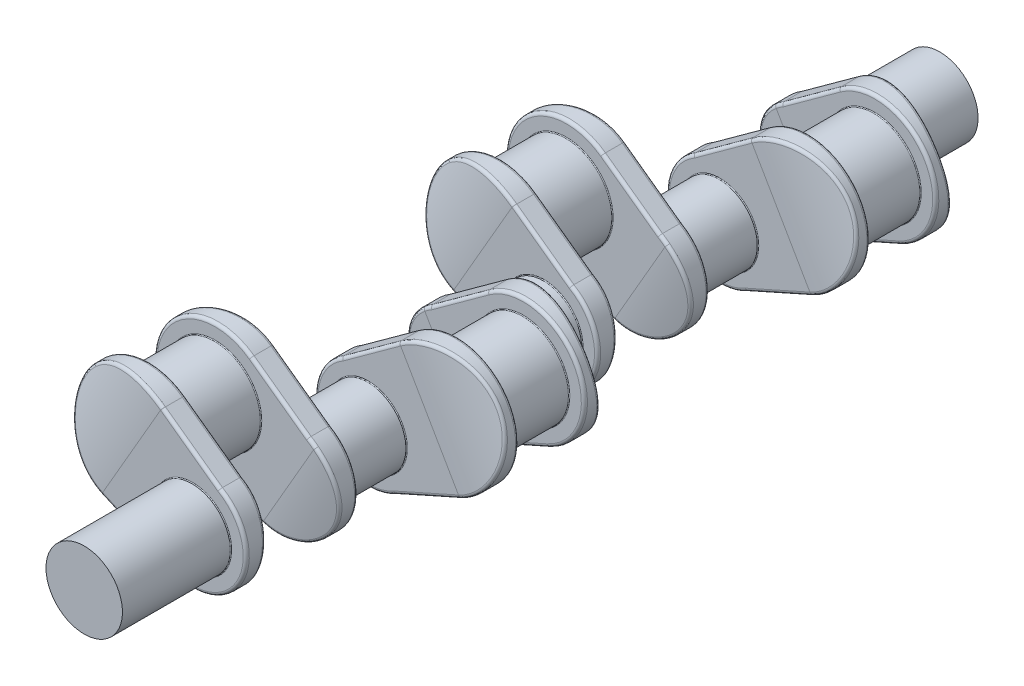
SolidWorks part; units mm, degrees
ref_plane "Front Plane" through (0, 0, 0) normal (0, 0, 1) x (1, 0, 0)
ref_plane "Top Plane" through (0, 0, 0) normal (0, 1, 0) x (1, 0, 0)
ref_plane "Right Plane" through (0, 0, 0) normal (1, 0, 0) x (0, 0, -1)
sketch "Sketch1" plane through (0, 0, 0) normal (0, 0, 1) x (1, 0, 0)
  circle A0 centre (0, 0) radius 38.1
  dimension "D1" = 76.2
extrude "Boss-Extrude1" add sketch "Sketch1" along normal blind 27.31
sketch "Sketch2" plane through (0, 0, 27.31) normal (0, 0, 1) x (1, 0, 0)
  line L0 (-44.45, 63.5) -> (-50.5257, 5.272)
  line L1 (44.45, 63.5) -> (50.5257, 5.272)
  arc A0 (-50.5257, 5.272) -> (50.5257, 5.272) centre (0, 0) ccw
  arc A1 (44.45, 63.5) -> (-44.45, 63.5) centre (0, 63.5) ccw
  circle A2 centre (0, 0) radius 38.1 construction
  point P9 (0, 0)
  dimension "D1" = 12.7
  dimension "D2" = 88.9
  dimension "D3" = 63.5
extrude "Boss-Extrude2" add sketch "Sketch2" along normal blind 19
sketch "Sketch3" plane through (0, 0, 46.31) normal (0, 0, 1) x (1, 0, 0)
  circle A1 centre (0, 63.5) radius 31.75
  dimension "D1" = 63.5
extrude "Boss-Extrude3" add sketch "Sketch3" along normal blind 26.67
sketch "Sketch4" plane through (0, 0, 0) normal (1, 0, 0) x (0, 0, -1)
  line L0 (-46.31, -50.8) -> (-27.31, -50.8) construction
  line L1 (-46.31, 5.272) -> (-58.1018, 5.272)
  line L2 (-58.1018, 5.272) -> (-58.1018, -50.8)
  line L3 (-58.1018, -50.8) -> (-36.81, -50.8)
  arc A0 (-46.31, 5.272) -> (-36.81, -50.8) centre (122.6899, 5.064) ccw
  dimension "D1" = 169
extrude "Cut-Extrude1" cut sketch "Sketch4" against normal mid plane 180.67
sketch "Sketch5" plane through (0, 0, 0) normal (1, 0, 0) x (0, 0, -1)
  line L0 (-27.31, 107.95) -> (-46.31, 107.95) construction
  line L1 (-32.31, 107.95) -> (-14.9237, 107.95)
  line L2 (-14.9237, 107.95) -> (-14.9237, 63.5)
  line L3 (-14.9237, 63.5) -> (-27.31, 63.5)
  arc A0 (-27.31, 63.5) -> (-32.31, 107.95) centre (-196.2738, 67.0002) ccw
  dimension "D2" = 169
  dimension "D1" = 5
extrude "Cut-Extrude2" cut sketch "Sketch5" against normal mid plane 180.67
fillet "Fillet1" radius 2.54 10 edges at (-47.4878, 34.386, 27.31) (0, -50.8, 27.31) (-47.4878, 34.386, 46.31) (-50.547, 5.0641, 46.31) (0.0331, -50.8, 36.81) (50.547, 5.0641, 46.31) (3.1078, 107.8412, 32.2829) (47.4878, 34.386, 27.31) (0, 107.95, 46.31) (47.4878, 34.386, 46.31)
fillet "Fillet2" radius 0.64 2 edges at (38.1, 0, 27.31) (31.75, 63.5, 46.31)
mirror "Mirror1" about plane through (0, 0, 0) normal (0, 0, 1) of bodies 105
ref_axis "Axis1" through (0, 63.5, 471.9753) along (0, 0, -1)
pattern_linear "LPattern1" count 4 spacing 145.96 along (0, 0, 1) of bodies 106
move or copy body "Body-Move/Copy1" bodies to move or copy 107 copy no rotation origin (0, 63.5, 0) rotation axis (0, 0, -1) rotation angle 120
move or copy body "Body-Move/Copy2" bodies to move or copy 109 copy no rotation origin (0, 63.5, 0) rotation axis (0, 0, -1) rotation angle 120
move or copy body "Body-Move/Copy3" bodies to move or copy 106 copy no rotation origin (0, 63.5, 0) rotation axis (0, 0, 1) rotation angle 120
move or copy body "Body-Move/Copy4" bodies to move or copy 108 copy no rotation origin (0, 63.5, 0) rotation axis (0, 0, 1) rotation angle 120
sketch "Sketch6" plane through (0, 0, 510.86) normal (0, 0, 1) x (1, 0, 0)
  circle A1 centre (0, 63.5) radius 31.75
  circle A2 centre (0, 63.5) radius 31.75
  dimension "D1" = 0
extrude "Boss-Extrude4" add sketch "Sketch6" along normal blind 63.5
sketch "Sketch7" plane through (0, 0, -72.98) normal (0, 0, -1) x (-1, 0, 0)
  circle A1 centre (0, 63.5) radius 31.75
  circle A2 centre (0, 63.5) radius 31.75
  dimension "D1" = 0
extrude "Boss-Extrude5" add sketch "Sketch7" along normal blind 63.5
combine bodies "Combine1" operation type add bodies to combine 114 113 110 115
